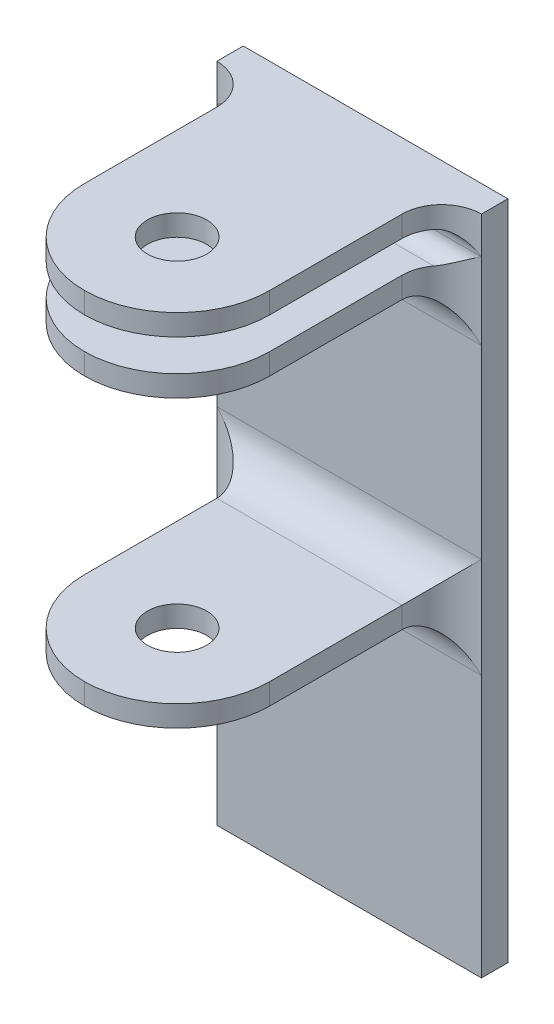
SolidWorks part; units mm, degrees
ref_plane "Plan de face" through (0, 0, 0) normal (1, 0, 0) x (0, 1, 0)
ref_plane "Plan de dessus" through (0, 0, 0) normal (0, 0, 1) x (0, 1, 0)
ref_plane "Plan de droite" through (0, 0, 0) normal (0, 1, 0) x (-1, 0, 0)
sketch "Esquisse1" plane through (0, 0, 0) normal (0, 0, 1) x (0, 1, 0)
  line L1 (0, 0) -> (250, 0)
  line L2 (0, 0) -> (0, 100)
  line L3 (0, 100) -> (250, 100)
  line L4 (250, 0) -> (250, 100)
  dimension "D1" = 250
  dimension "D2" = 100
extrude "Boss.-Extru.1" add sketch "Esquisse1" along normal blind 10
sketch "Esquisse2" plane through (0, 0, 10) normal (0, 0, 1) x (1, 0, 0)
  line L0 (-100, 250) -> (-100, 0) construction
  line L1 (-85, 230) -> (-15, 230)
  line L2 (-85, 230) -> (-85, 222)
  line L3 (-85, 222) -> (-15, 222)
  line L4 (-15, 230) -> (-15, 222)
  line L5 (-85, 250) -> (-15, 250)
  line L6 (0, 0) -> (0, 250) construction
  line L7 (0, 250) -> (-100, 250) construction
  line L8 (-85, 122) -> (-15, 122)
  line L9 (-85, 122) -> (-85, 114)
  line L10 (-85, 114) -> (-15, 114)
  line L11 (-15, 122) -> (-15, 114)
  line L12 (-85, 250) -> (-85, 242)
  line L13 (-85, 242) -> (-15, 242)
  line L14 (-15, 250) -> (-15, 242)
  dimension "D1" = 8
  dimension "D2" = 8
  dimension "D3" = 100
  dimension "D4" = 70
  dimension "D5" = 15
  dimension "D6" = 70
  dimension "D7" = 15
  dimension "D8" = 12
  dimension "D9" = 70
  dimension "D10" = 8
  dimension "D11" = 15
extrude "Boss.-Extru.2" add sketch "Esquisse2" along normal blind 100
fillet "Congé1" radius 35 6 edges at (-85, 226, 110) (-15, 226, 110) (-15, 118, 110) (-85, 118, 110) (-85, 246, 110) (-15, 246, 110)
sketch "Esquisse3" plane through (0, 250, 0) normal (0, 1, 0) x (-1, 0, 0)
  line L0 (0, 10) -> (0, 0) construction
  line L2 (0, 0) -> (100, 0) construction
  circle A0 centre (50, 75) radius 11.2
  dimension "D3" = 22.4
  dimension "D1" = 50
  dimension "D2" = 75
extrude "Enlèv. mat.-Extru.1" cut sketch "Esquisse3" against normal blind 150
fillet "Congé2" radius 15 9 edges at (-15, 118, 10) (-50, 122, 10) (-85, 118, 10) (-50, 114, 10) (-85, 246, 10) (-15, 246, 10) (-15, 226, 10) (-50, 222, 10) (-85, 226, 10)
fillet "Congé3" radius 6 2 edges at (-50, 242, 10) (-50, 230, 10)
sketch "Esquisse4" plane through (0, 0, 0) normal (0, 0, -1) x (1, 0, 0)
  line L0 (0, 0) -> (0, -250) construction
  line L1 (-100, 0) -> (0, 0)
  line L2 (-100, 0) -> (-100, -250)
  line L3 (-100, -250) -> (0, -250)
  line L4 (0, 0) -> (0, -250)
